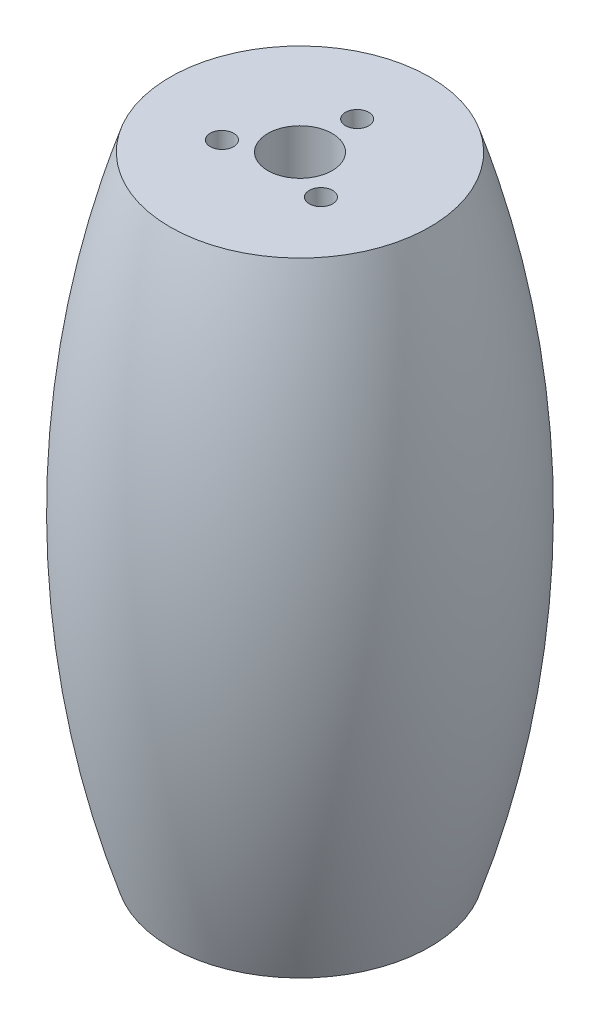
SolidWorks part; units mm, degrees
ref_plane "正面" through (0, 0, 0) normal (0, 0, 1) x (1, 0, 0)
ref_plane "平面" through (0, 0, 0) normal (0, 1, 0) x (1, 0, 0)
ref_plane "右側面" through (0, 0, 0) normal (1, 0, 0) x (0, 0, -1)
sketch "ｽｹｯﾁ1" plane through (0, 0, 0) normal (0, 0, 1) x (1, 0, 0)
  line L0 (-25, 0) -> (0, 0)
  line L1 (0, 0) -> (0, 120)
  line L2 (0, 120) -> (-25, 120)
  arc A0 (-25, 0) -> (-25, 120) centre (160, 60) cw
  dimension "D1" = 120
  dimension "D2" = 25
  dimension "D3" = 25
  dimension "D4" = 160
revolve "回転1" add sketch "ｽｹｯﾁ1" angle 360 about L1
sketch "ｽｹｯﾁ2" plane through (0, 120, 0) normal (0, 1, 0) x (1, 0, 0)
  line L0 (0, 0) -> (0, 11) construction
  line L1 (-9.5263, -5.5) -> (0, 0) construction
  line L2 (0, 0) -> (9.5263, -5.5) construction
  circle A0 centre (0, 11) radius 2.25
  circle A1 centre (9.5263, -5.5) radius 2.25
  circle A2 centre (-9.5263, -5.5) radius 2.25
  dimension "D1" = 4.5
  dimension "D2" = 11
  dimension "D3" = 3
extrude "ｶｯﾄ - 押し出し1" cut sketch "ｽｹｯﾁ2" against normal blind 5
ref_plane "平面1" through (0, 60, 0) normal (0, 1, 0) x (1, 0, 0)
mirror "ﾐﾗｰ1" about plane through (0, 60, 0) normal (0, 1, 0) of "ｶｯﾄ - 押し出し1"
sketch "ｽｹｯﾁ3" plane through (0, 120, 0) normal (0, 1, 0) x (1, 0, 0)
  circle A0 centre (0, 0) radius 6.2
  dimension "D1" = 12.4
extrude "ｶｯﾄ - 押し出し2" cut sketch "ｽｹｯﾁ3" against normal through all
